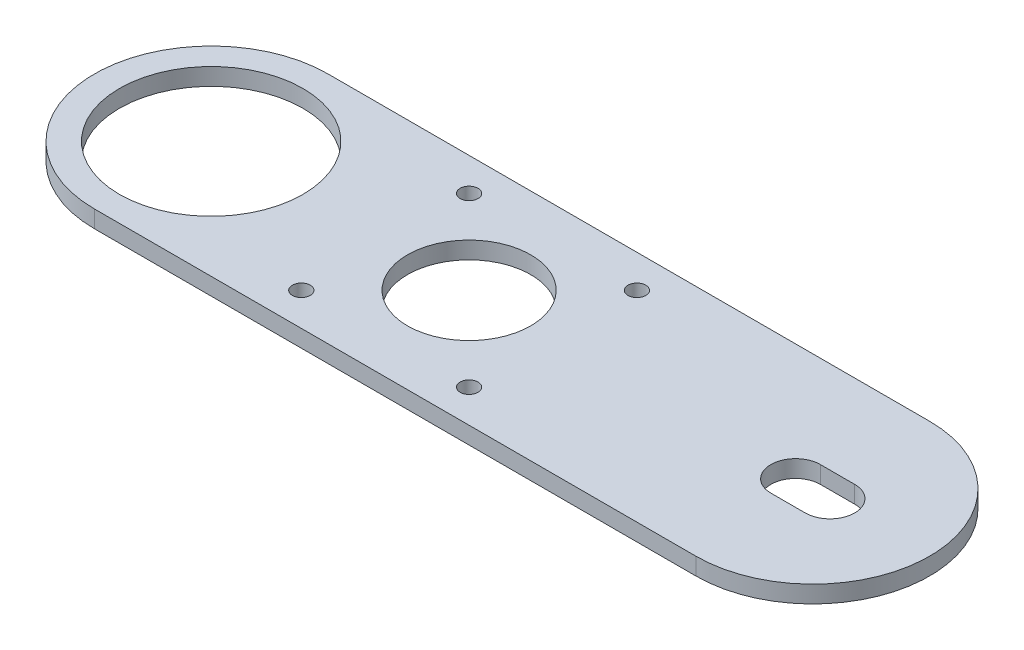
SolidWorks part; units mm, degrees
ref_plane "Front Plane" through (0, 0, 0) normal (0, 0, 1) x (1, 0, 0)
ref_plane "Top Plane" through (0, 0, 0) normal (0, 1, 0) x (1, 0, 0)
ref_plane "Right Plane" through (0, 0, 0) normal (1, 0, 0) x (0, 0, -1)
sketch "Sketch1" plane through (0, 0, 0) normal (0, 1, 0) x (1, 0, 0)
  line L0 (0, 0) -> (111.1504, 0) construction
  line L1 (0, 21.59) -> (111.1504, 21.59)
  line L2 (0, -21.59) -> (111.1504, -21.59)
  line L3 (55.5752, 21.59) -> (55.5752, -21.59) construction
  line L4 (0, 0) -> (111.1504, 0) construction
  line L5 (32.1504, -15.5) -> (63.1504, -15.5) construction
  line L6 (32.1504, -15.5) -> (32.1504, 15.5) construction
  line L7 (32.1504, 15.5) -> (63.1504, 15.5) construction
  line L8 (63.1504, -15.5) -> (63.1504, 15.5) construction
  line L9 (32.1504, -15.5) -> (63.1504, 15.5) construction
  line L10 (32.1504, 15.5) -> (63.1504, -15.5) construction
  line L11 (32.1504, 0) -> (63.1504, 0) construction
  line L12 (47.6504, -15.5) -> (47.6504, 15.5) construction
  arc A0 (0, 21.59) -> (0, -21.59) centre (0, 0) ccw
  arc A1 (111.1504, -21.59) -> (111.1504, 21.59) centre (111.1504, 0) ccw
  circle A2 centre (0, 0) radius 16.9545
  circle A3 centre (111.1504, 0) radius 4.572
  circle A4 centre (47.6504, 0) radius 11.381
  circle A5 centre (32.1504, -15.5) radius 1.651
  circle A6 centre (32.1504, 15.5) radius 1.651
  circle A7 centre (63.1504, 15.5) radius 1.651
  circle A8 centre (63.1504, -15.5) radius 1.651
  point P3 (55.5752, 0)
  dimension "D2" = 21.59
  dimension "D3" = 33.909
  dimension "D4" = 9.144
  dimension "D5" = 22.762
  dimension "D7" = 3.302
  dimension "D10" = 3.302
  dimension "D1" = 111.1504
  dimension "D6" = 63.5
  dimension "D8" = 31
  dimension "D9" = 31
extrude "Boss-Extrude1" add sketch "Sketch1" along normal blind 3.175
sketch "Sketch2" plane through (0, 3.175, 0) normal (0, 1, 0) x (1, 0, 0)
  line L0 (114.3254, 0) -> (107.9754, 0) construction
  line L1 (114.3254, -4.572) -> (107.9754, -4.572)
  line L2 (114.3254, 4.572) -> (107.9754, 4.572)
  circle A0 centre (111.1504, 0) radius 4.572 construction
  circle A1 centre (111.1504, 0) radius 4.572 construction
  arc A2 (114.3254, -4.572) -> (114.3254, 4.572) centre (114.3254, 0) ccw
  arc A3 (107.9754, 4.572) -> (107.9754, -4.572) centre (107.9754, 0) ccw
  point P6 (111.1504, 0)
  dimension "D1" = 3.175
  dimension "D2" = 3.175
extrude "Cut-Extrude1" cut sketch "Sketch2" against normal through all
